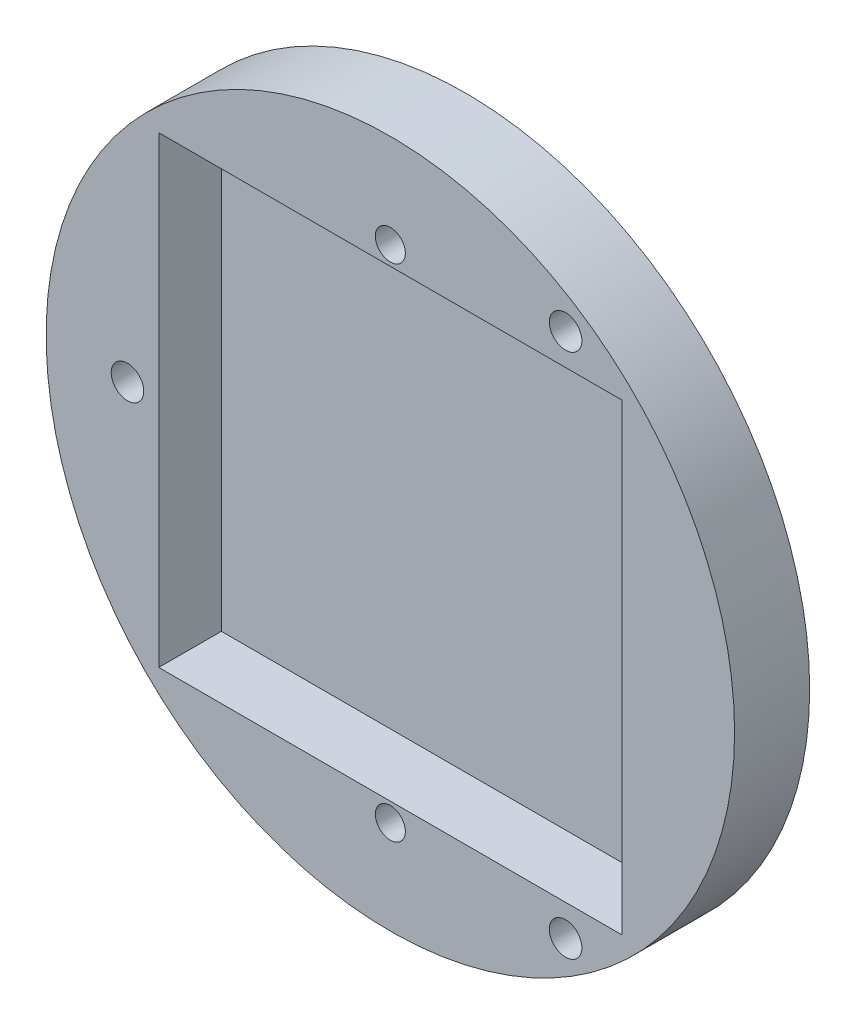
SolidWorks part; units mm, degrees
material "Nylon 101"
ref_plane "Front Plane" through (0, 0, 0) normal (0, 0, 1) x (1, 0, 0)
ref_plane "Top Plane" through (0, 0, 0) normal (0, 1, 0) x (1, 0, 0)
ref_plane "Right Plane" through (0, 0, 0) normal (1, 0, 0) x (0, 0, -1)
sketch "Sketch1" plane through (0, 0, 0) normal (0, 0, 1) x (1, 0, 0)
  line L1 (-18.5, 18.5) -> (18.5, 18.5)
  line L2 (-18.5, 18.5) -> (-18.5, -18.5)
  line L3 (-18.5, -18.5) -> (18.5, -18.5)
  line L4 (18.5, 18.5) -> (18.5, -18.5)
  line L5 (-18.5, 18.5) -> (18.5, -18.5) construction
  line L6 (-18.5, -18.5) -> (18.5, 18.5) construction
  line L7 (-17.5, 17.5) -> (17.5, 17.5)
  line L8 (-17.5, 17.5) -> (-17.5, -17.5)
  line L9 (-17.5, -17.5) -> (17.5, -17.5)
  line L10 (17.5, 17.5) -> (17.5, -17.5)
  line L11 (-17.5, 17.5) -> (17.5, -17.5) construction
  line L12 (-17.5, -17.5) -> (17.5, 17.5) construction
  circle A0 centre (0, 0) radius 27.5
  point P4 (0, 0)
  point P9 (0, 0)
  dimension "D1" = 55
  dimension "D2" = 37
  dimension "D3" = 37
  dimension "D4" = 1
  dimension "D5" = 1
extrude "Boss-Extrude1" add sketch "Sketch1" along normal blind 6 contours A0 L1 L4 L3 L2 region at (-26.7222, 0, 0)
extrude "Boss-Extrude2" add sketch "Sketch1<3>" along normal blind 1 contours L10 L7 L8 L9 | L4 L1 L2 L3 L7 L10 L9 L8 region at (0, 17.9767, 0) region at (0, 0, 0)
sketch "Sketch1<3>" plane through (0, 0, 0) normal (0, 0, 1) x (1, 0, 0) same geometry as "Sketch1"
sketch "Sketch2" plane through (0, 0, 0) normal (0, 1, 0) x (1, 0, 0)
  line L4 (0, 15) -> (0, -15) construction
  line L5 (0, 6.5) -> (0, 0)
  line L6 (0, 0) -> (-6.5, 0)
  arc A1 (0, 6.5) -> (-6.5, 0) centre (0, 0) ccw
  dimension "D1" = 13
  dimension "D4" = 30
revolve "Revolve1" add sketch "Sketch2" angle 360 about L4
hole_wizard "M2 Clearance Hole1" positions "Sketch3" profile "Sketch4" hole size "M2" standard "ANSI Metric" end condition through all
sketch "Sketch3" plane through (0, 0, 6) normal (0, 0, 1) x (1, 0, 0)
  line L4 (-18.5, 18.5) -> (-18.5, -18.5) construction
  line L5 (-18.5, 18.5) -> (18.5, 18.5) construction
  line L6 (-18.5, -18.5) -> (18.5, -18.5) construction
  line L7 (18.5, 18.5) -> (18.5, -18.5) construction
  point P0 (-21, 0)
  point P2 (14, -21)
  point P4 (14, 21)
  dimension "D2" = 2.5
  dimension "D1" = 2.5
  dimension "D3" = 2.5
  dimension "D4" = 4.5
sketch "Sketch4" plane through (-21, 0, 6) normal (1, 0, 0) x (0, -1, 0)
  line L0 (0, 0) -> (0, 12.5)
  line L1 (0, 12.5) -> (1.3, 12.5)
  line L2 (1.3, 12.5) -> (1.3, 0)
  line L5 (1.3, 0) -> (0, 0)
  line L11 (0, -6.35) -> (0, 107.95) construction
  dimension "Thru Hole Dia." = 2.6
  dimension "Thru Hole Depth" = 12.5
sketch "Sketch5" plane through (0, 0, 0) normal (0, 0, 1) x (1, 0, 0)
  line L0 (18.5, 18.5) -> (18.5, -18.5) construction
  line L1 (-18.5, -18.5) -> (18.5, -18.5) construction
  line L2 (-18.5, 18.5) -> (18.5, 18.5) construction
  line L3 (6.875, 0) -> (-6.875, 0) construction
  line L4 (0, 17.4019) -> (2.25, 18.701)
  line L5 (2.25, 18.701) -> (2.25, 21.299)
  line L6 (2.25, 21.299) -> (0, 22.5981)
  line L7 (0, 22.5981) -> (-2.25, 21.299)
  line L8 (-2.25, 21.299) -> (-2.25, 18.701)
  line L9 (-2.25, 18.701) -> (0, 17.4019)
  line L10 (-2.25, -18.701) -> (0, -17.4019)
  line L11 (-2.25, -21.299) -> (-2.25, -18.701)
  line L12 (0, -22.5981) -> (-2.25, -21.299)
  line L13 (2.25, -21.299) -> (0, -22.5981)
  line L14 (2.25, -18.701) -> (2.25, -21.299)
  line L15 (0, -17.4019) -> (2.25, -18.701)
  circle A0 centre (0, 20) radius 2.25 construction
  circle A1 centre (0, -20) radius 2.25 construction
  point P0 (0, 20)
  point P1 (0, -20)
  point P26 (0, -20)
  dimension "D1" = 18.5
  dimension "D2" = 1.5
  dimension "D3" = 1.5
  dimension "D4" = 4.5
hole_wizard "M2 Clearance Hole2" positions "3DSketch1" profile "Sketch7" hole size "M2" standard "ANSI Metric" end condition through all
sketch3d "3DSketch1"
  point P0 (0, 20, 0)
  point P3 (0, -20, 0)
sketch "Sketch7" plane through (0, 20, 0) normal (1, 0, 0) x (0, 1, 0)
  line L0 (0, 0) -> (0, 6)
  line L1 (0, 6) -> (1.2, 6)
  line L2 (1.2, 6) -> (1.2, 0)
  line L5 (1.2, 0) -> (0, 0)
  line L11 (0, -6.35) -> (0, 107.95) construction
  dimension "Thru Hole Dia." = 2.4
  dimension "Thru Hole Depth" = 6
extrude "Cut-Extrude3" cut sketch "Sketch5" along normal blind 0.8
